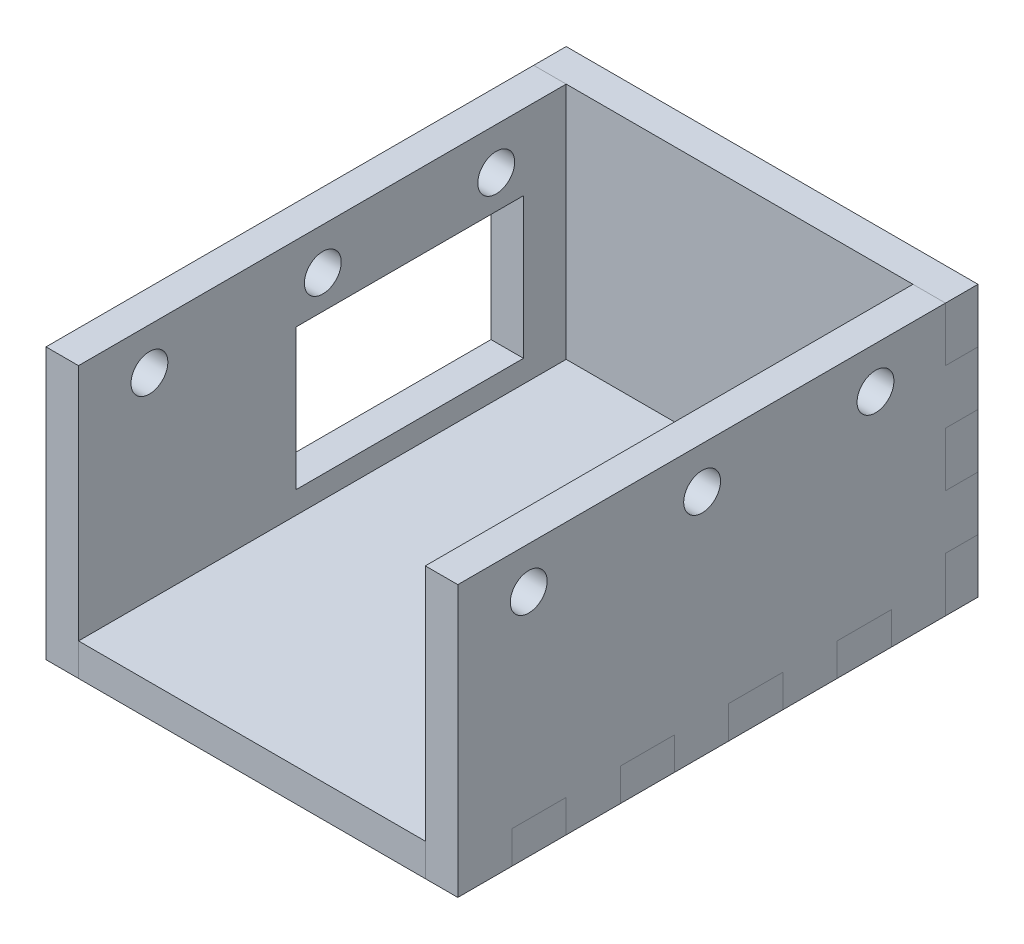
SolidWorks part; units mm, degrees
ref_plane "Front Plane" through (0, 0, 0) normal (0, 0, 1) x (1, 0, 0)
ref_plane "Top Plane" through (0, 0, 0) normal (0, 1, 0) x (1, 0, 0)
ref_plane "Right Plane" through (0, 0, 0) normal (1, 0, 0) x (0, 0, -1)
sketch "Sketch1" plane through (0, 0, 0) normal (0, 1, 0) x (1, 0, 0)
  line L33 (0, 0) -> (5, 0)
  line L34 (5, 0) -> (5, 3)
  line L54 (5, 3) -> (10, 3)
  line L55 (10, 3) -> (10, 0)
  line L56 (10, 0) -> (15, 0)
  line L57 (15, 0) -> (15, 3)
  line L58 (15, 3) -> (20, 3)
  line L59 (20, 3) -> (20, 0)
  line L60 (20, 0) -> (25, 0)
  line L61 (25, 0) -> (25, 3)
  line L62 (25, 3) -> (30, 3)
  line L63 (30, 3) -> (30, 0)
  line L64 (30, 0) -> (32, 0)
  line L65 (32, 0) -> (32, -5)
  line L66 (32, -5) -> (35, -5)
  line L67 (35, -5) -> (35, -10)
  line L68 (35, -10) -> (32, -10)
  line L69 (32, -10) -> (32, -15)
  line L70 (32, -15) -> (35, -15)
  line L71 (35, -15) -> (35, -20)
  line L72 (35, -20) -> (32, -20)
  line L73 (32, -20) -> (32, -25)
  line L74 (32, -25) -> (35, -25)
  line L75 (35, -25) -> (35, -30)
  line L76 (35, -30) -> (32, -30)
  line L77 (32, -30) -> (32, -35)
  line L78 (32, -35) -> (35, -35)
  line L79 (35, -35) -> (35, -40)
  line L80 (35, -40) -> (32, -40)
  line L81 (32, -40) -> (32, -45)
  line L82 (16, -1020.6314) -> (16, 48979.3686) construction
  line L83 (0, -40) -> (0, -45)
  line L84 (-3, -40) -> (0, -40)
  line L85 (-3, -35) -> (-3, -40)
  line L86 (0, -35) -> (-3, -35)
  line L87 (0, -30) -> (0, -35)
  line L88 (-3, -30) -> (0, -30)
  line L89 (-3, -25) -> (-3, -30)
  line L90 (0, -25) -> (-3, -25)
  line L91 (0, -20) -> (0, -25)
  line L92 (-3, -20) -> (0, -20)
  line L93 (-3, -15) -> (-3, -20)
  line L94 (0, -15) -> (-3, -15)
  line L95 (0, -10) -> (0, -15)
  line L96 (-3, -10) -> (0, -10)
  line L97 (-3, -5) -> (-3, -10)
  line L98 (0, -5) -> (-3, -5)
  line L99 (0, 0) -> (0, -5)
  line L100 (2, 0) -> (0, 0)
  line L101 (0, -45) -> (32, -45)
  point P21 (32, -2.5)
  dimension "D1" = 4
  dimension "D2" = 16
extrude "Boss-Extrude1" add sketch "Sketch1" along normal blind 3 contours L98 L83 L96 L95 L94 L93 L92 L91 L90 L89 L88 L87 L86 | L98 L73 L72 L71 L69 L63 L61 L67 region at (16.0421, 0, 21.8271)
sketch "Sketch4" plane through (32, 0, 0) normal (1, 0, 0) x (0, 0, -1)
  line L0 (-5, 3) -> (-5, 0)
  line L1 (-5, 0) -> (0, 0)
  line L2 (0, 0) -> (0, 3)
  line L3 (-5, 3) -> (-10, 3)
  line L4 (-15, 3) -> (-15, 0)
  line L5 (-15, 0) -> (-10, 0)
  line L6 (-10, 0) -> (-10, 3)
  line L7 (-15, 3) -> (-20, 3)
  line L8 (-25, 3) -> (-25, 0)
  line L9 (-25, 0) -> (-20, 0)
  line L10 (-20, 0) -> (-20, 3)
  line L11 (-25, 3) -> (-30, 3)
  line L12 (-35, 3) -> (-35, 0)
  line L13 (-35, 0) -> (-30, 0)
  line L14 (-30, 0) -> (-30, 3)
  line L15 (-35, 3) -> (-40, 3)
  line L16 (-40, 3) -> (-40, 0)
  line L17 (-40, 3) -> (-40, 0) construction
  line L18 (-40, 0) -> (-45, 0)
  line L19 (-45, 0) -> (-45, 3)
  line L20 (-45, 3) -> (-45, 25)
  line L21 (-45, 25) -> (0, 25)
  line L22 (0, 25) -> (0, 20)
  line L23 (0, 20) -> (3, 20)
  line L24 (3, 20) -> (3, 15)
  line L25 (3, 15) -> (0, 15)
  line L26 (0, 15) -> (0, 10)
  line L27 (0, 10) -> (3, 10)
  line L28 (3, 10) -> (3, 5)
  line L29 (3, 5) -> (0, 5)
  line L30 (0, 3) -> (0, 5)
  dimension "D1" = 22
extrude "Boss-Extrude2" add sketch "Sketch4" along normal blind 3 separate body
ref_plane "Plane1" through (16, 0, 0) normal (-1, 0, 0) x (0, 0, 1)
mirror "Mirror1" about plane through (16, 0, 0) normal (-1, 0, 0) of bodies 102
sketch "Sketch5" plane through (0, 0, 0) normal (0, 0, -1) x (-1, 0, 0)
  line L0 (-35, 25) -> (3, 25)
  line L1 (3, 25) -> (3, 20)
  line L2 (3, 20) -> (0, 20)
  line L3 (0, 20) -> (0, 15)
  line L4 (0, 15) -> (3, 15)
  line L5 (3, 15) -> (3, 10)
  line L6 (3, 10) -> (0, 10)
  line L7 (0, 10) -> (0, 5)
  line L8 (0, 5) -> (3, 5)
  line L9 (3, 5) -> (3, 0)
  line L10 (3, 0) -> (0, 0)
  line L11 (-5, 0) -> (-5, 3)
  line L12 (-5, 3) -> (-10, 3)
  line L13 (-10, 3) -> (-10, 0)
  line L14 (0, 0) -> (-5, 0)
  line L15 (-15, 0) -> (-15, 3)
  line L16 (-15, 3) -> (-20, 3)
  line L17 (-20, 3) -> (-20, 0)
  line L18 (-10, 0) -> (-15, 0)
  line L19 (-25, 0) -> (-25, 3)
  line L20 (-25, 3) -> (-30, 3)
  line L21 (-30, 3) -> (-30, 0)
  line L22 (-20, 0) -> (-25, 0)
  line L23 (-30, 0) -> (-32, 0)
  line L24 (-35, 0) -> (-35, 5)
  line L25 (-35, 5) -> (-32, 5)
  line L26 (-32, 5) -> (-32, 10)
  line L27 (-32, 10) -> (-35, 10)
  line L28 (-35, 10) -> (-35, 15)
  line L29 (-35, 15) -> (-32, 15)
  line L30 (-32, 15) -> (-32, 20)
  line L31 (-32, 20) -> (-35, 20)
  line L32 (-35, 20) -> (-35, 25)
  line L33 (-32, 0) -> (-35, 0)
  point P0 (-35, 0)
  point P27 (0, 0)
  dimension "D1" = 3
extrude "Boss-Extrude3" add sketch "Sketch5" along normal blind 3 separate body
sketch "Sketch6" plane through (-3, 0, 0) normal (-1, 0, 0) x (0, 0, 1)
  circle A0 centre (6.4572, 21.156) radius 1.7
  circle A1 centre (22.4572, 21.156) radius 1.7
  circle A2 centre (38.4572, 21.156) radius 1.7
  point P2 (3.3884, 17.5611)
  dimension "D1" = 3
extrude "Cut-Extrude1" cut sketch "Sketch6" against normal blind 44
sketch "Sketch8" plane through (-3, 0, 0) normal (-1, 0, 0) x (0, 0, 1)
  line L1 (3.9391, 5.0533) -> (24.9391, 5.0533)
  line L2 (3.9391, 5.0533) -> (3.9391, 18.0533)
  line L3 (3.9391, 18.0533) -> (24.9391, 18.0533)
  line L4 (24.9391, 5.0533) -> (24.9391, 18.0533)
  point P4 (3.9128, 5.1239)
  point P5 (3.9391, 5.0533)
  dimension "D1" = 13
  dimension "D2" = 21
extrude "Cut-Extrude2" cut sketch "Sketch8" against normal blind 5
equation "\"hardboard_thickness\"=3"
equation "\"D1@Boss-Extrude1\"=\"hardboard_thickness\""
equation "\"D1@Boss-Extrude2\"=\"hardboard_thickness\""
